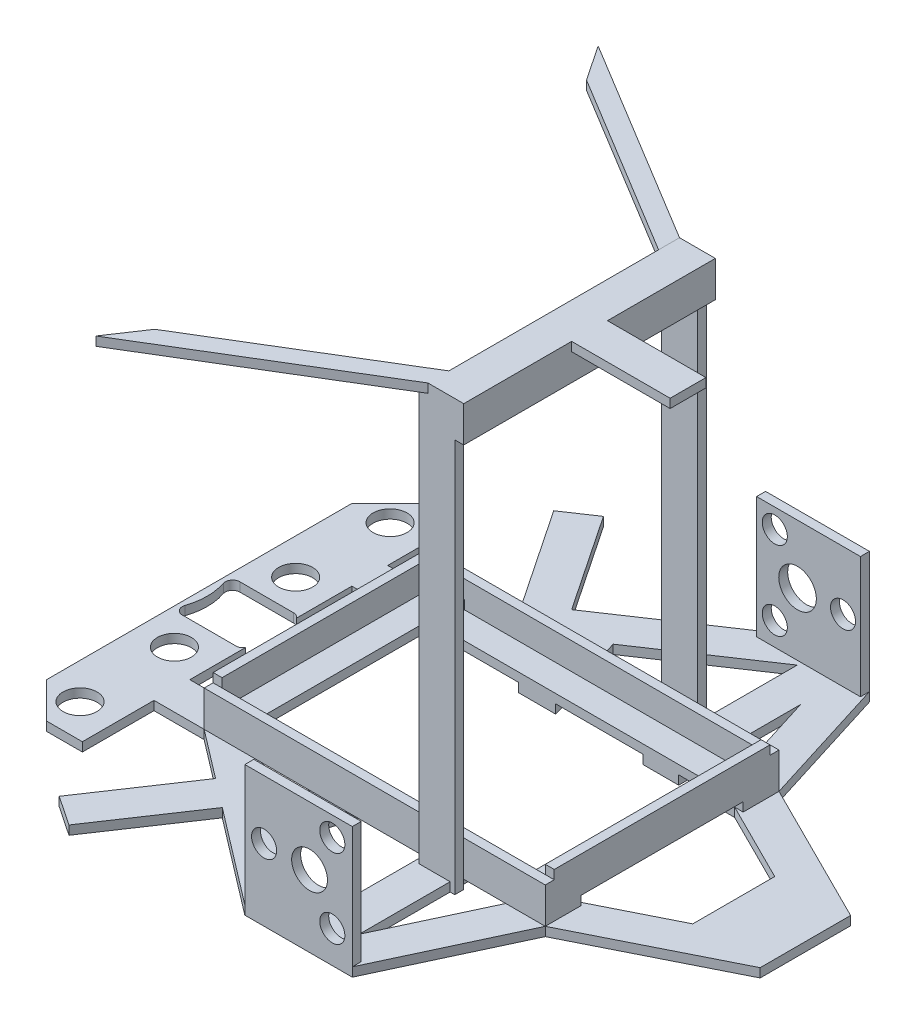
SolidWorks part; units mm, degrees
material "Galvanized Steel"
ref_plane "Front Plane" through (0, 0, 0) normal (0, 0, 1) x (1, 0, 0)
ref_plane "Top Plane" through (0, 0, 0) normal (0, 1, 0) x (1, 0, 0)
ref_plane "Right Plane" through (0, 0, 0) normal (1, 0, 0) x (0, 0, -1)
sketch "Battery Front sketch" plane through (0, 0, 0) normal (0, 0, 1) x (1, 0, 0)
  line L0 (90.25, 144.5) -> (90.25, 4) construction
  line L1 (90.25, 15) -> (95.25, 15)
  line L2 (90.25, 15) -> (90.25, -5)
  line L3 (90.25, -5) -> (95.25, -5)
  line L4 (95.25, 15) -> (95.25, -5)
  line L5 (86.25, 0) -> (-86.25, 0) construction
  line L6 (75.25, 0) -> (95.25, 0)
  line L7 (75.25, 0) -> (75.25, -5)
  line L8 (75.25, -5) -> (95.25, -5)
  line L9 (95.25, 0) -> (95.25, -5)
  dimension "D1" = 20
  dimension "D2" = 20
  dimension "D3" = 5
  dimension "D4" = 5
extrude "Battery Front" add sketch "Battery Front sketch" against normal up to surface (120.5 mm away) contours L3 L2 L1 L4 | L8 L7 L6 L9
sketch "Battery Rear Sketch" plane through (0, 0, -120.5) normal (0, 0, -1) x (-1, 0, 0)
  line L0 (90.25, 144.5) -> (90.25, 4) construction
  line L1 (90.25, 15) -> (95.25, 15)
  line L2 (90.25, 15) -> (90.25, -5)
  line L3 (90.25, -5) -> (95.25, -5)
  line L4 (95.25, 15) -> (95.25, -5)
  line L5 (86.25, 0) -> (-86.25, 0) construction
  line L6 (75.25, 0) -> (95.25, 0)
  line L7 (75.25, 0) -> (75.25, -5)
  line L8 (75.25, -5) -> (95.25, -5)
  line L9 (95.25, 0) -> (95.25, -5)
  dimension "D1" = 5
  dimension "D2" = 5
  dimension "D3" = 20
  dimension "D4" = 20
extrude "Battery Rear" add sketch "Battery Rear Sketch" against normal up to surface (120.5 mm away) separate body contours L2 L6 L4 L1 | L8 L7 L6 L9 | L4 L1 L2 L3 region at (-92.75, 7.5, -120.5)
sketch "Battery Side Sketch" plane through (-95.25, 0, 0) normal (-1, 0, 0) x (0, 0, 1)
  line L0 (0, 144.5) -> (0, 4) construction
  line L1 (0, 10) -> (5, 10)
  line L2 (0, 10) -> (0, -10)
  line L3 (0, -10) -> (5, -10)
  line L4 (5, 10) -> (5, -10)
  line L5 (0, -5) -> (-120.5, -5) construction
  line L6 (5, -10) -> (-15, -10)
  line L7 (5, -10) -> (5, -5)
  line L8 (5, -5) -> (-15, -5)
  line L9 (-15, -10) -> (-15, -5)
  line L10 (-120.5, 15) -> (-120.5, -5) construction
  line L11 (-120.5, 10) -> (-125.5, 10)
  line L12 (-120.5, 10) -> (-120.5, -10)
  line L13 (-120.5, -10) -> (-125.5, -10)
  line L14 (-125.5, 10) -> (-125.5, -10)
  line L16 (-105.5, -5) -> (-125.5, -5)
  line L17 (-105.5, -5) -> (-105.5, -10)
  line L18 (-105.5, -10) -> (-125.5, -10)
  line L19 (-125.5, -5) -> (-125.5, -10)
  line M10 (-120.5, -5) -> (0, -5)
  dimension "D1" = 20
  dimension "D2" = 20
  dimension "D3" = 20
  dimension "D4" = 20
  dimension "D5" = 5
  dimension "D6" = 5
  dimension "D7" = 5
  dimension "D8" = 5
extrude "Battery Side" add sketch "Battery Side Sketch" against normal up to surface (190.5 mm away) contours L9 L6 L2 M10 | L3 L2 L1 L4 | L14 L11 L12 L13 | L18 L17 L16 L19 region at (-95.25, -7.5, -7.5) up to face at (95.25, 5, -60.25)
sketch "Left Motor Attach Sketch" plane through (0, 0, -194) normal (0, 0, -1) x (-1, 0, 0)
  line L0 (-95.25, -10) -> (95.25, -10) construction
  line L1 (-14.2679, -10) -> (-72.2679, -10)
  line L2 (-14.2679, -10) -> (-14.2679, 57.8525)
  line L3 (-14.2679, 57.8525) -> (-72.2679, 57.8525)
  line L4 (-72.2679, -10) -> (-72.2679, 57.8525)
  arc A0 (-32.3069, 57.4983) -> (-39.0041, 57.7983) centre (-37.1179, 25.0025) ccw construction
  circle A1 centre (-24.4179, 46.9995) radius 7
  circle A2 centre (-62.5179, 25.0025) radius 7
  circle A3 centre (-24.4179, 3.0054) radius 7
  circle A4 centre (-37.1179, 25.0025) radius 10.5
  circle A5 centre (-24.4179, 46.9995) radius 4.8649 construction
  circle A6 centre (-62.5179, 25.0025) radius 4.8649 construction
  dimension "D3" = 14
  dimension "D4" = 14
  dimension "D5" = 14
  dimension "D6" = 21
  dimension "D1" = 58
  dimension "D2" = 10
extrude "Left Motor Attach" add sketch "Left Motor Attach Sketch" along normal blind 5 separate body
sketch "Right Motor Attach Sketch" plane through (0, 0, 73.5) normal (0, 0, 1) x (1, 0, 0)
  line L0 (95.25, -10) -> (-95.25, -10) construction
  line L1 (0.9679, -10) -> (60.9679, -10)
  line L2 (0.9679, -10) -> (0.9679, 57.8525)
  line L3 (0.9679, 57.8525) -> (60.9679, 57.8525)
  line L4 (60.9679, -10) -> (60.9679, 57.8525)
  line L5 (14.2679, 57.8525) -> (72.2679, 57.8525) construction
  circle A0 centre (49.8179, 46.9995) radius 7
  circle A1 centre (49.8179, 3.0054) radius 7
  circle A2 centre (11.7179, 25.0025) radius 7
  circle A3 centre (11.7179, 25.0025) radius 4.8649 construction
  circle A4 centre (37.1179, 25.0025) radius 10
  dimension "D1" = 14
  dimension "D2" = 14
  dimension "D3" = 14
  dimension "D4" = 20
  dimension "D5" = 60
  dimension "D6" = 9
extrude "Right Motor Attach" add sketch "Right Motor Attach Sketch" along normal blind 5 separate body
sketch "Support Sketch" plane through (0, -10, 0) normal (0, -1, 0) x (-1, 0, 0)
  line L0 (-14.2679, 199) -> (95.25, 125.5)
  line L1 (-95.25, 125.5) -> (95.25, 125.5) construction
  line L4 (89.1609, 105.5) -> (-50.1578, 199)
  line L5 (-72.2679, 199) -> (-14.2679, 199) construction
  line L6 (-50.1578, 199) -> (-14.2679, 199)
  line L7 (89.1609, 105.5) -> (95.25, 105.5)
  line L8 (95.25, 105.5) -> (95.25, 125.5)
  line L9 (-95.25, 105.5) -> (95.25, 105.5) construction
  line L10 (95.25, -5) -> (-0.9679, -78.5)
  line L11 (-0.9679, -78.5) -> (-33.9145, -78.5)
  line L12 (-0.9679, -78.5) -> (-60.9679, -78.5) construction
  line L13 (-33.9145, -78.5) -> (88.4851, 15)
  line L14 (-95.25, 15) -> (95.25, 15) construction
  line L15 (88.4851, 15) -> (95.25, 15)
  line L16 (95.25, 15) -> (95.25, -5)
  dimension "D1" = 20
  dimension "D2" = 20
extrude "Support" add sketch "Support Sketch" along normal blind 5
sketch "Support to motor sketch 1" plane through (0, -10, 0) normal (0, -1, 0) x (-1, 0, 0)
  line L0 (-60.9679, -78.5) -> (-95.25, -5)
  line L1 (-95.25, -5) -> (-95.25, 15)
  line L2 (-82.5099, 15) -> (-38.8993, -78.5)
  line L3 (-95.25, 15) -> (88.4851, 15) construction
  line L4 (-0.9679, -78.5) -> (-60.9679, -78.5) construction
  line L5 (-38.8993, -78.5) -> (-60.9679, -78.5)
  line L6 (-95.25, 15) -> (-82.5099, 15)
  line L7 (-95.25, 125.5) -> (-72.2679, 199)
  line L8 (-72.2679, 199) -> (-51.313, 199)
  line L9 (-72.2679, 199) -> (-50.1578, 199) construction
  line L10 (-51.313, 199) -> (-80.5487, 105.5)
  line L11 (-95.25, 105.5) -> (89.1609, 105.5) construction
  line L12 (-80.5487, 105.5) -> (-95.25, 105.5)
  line L13 (-95.25, 105.5) -> (-95.25, 125.5)
  dimension "D1" = 20
  dimension "D2" = 20
extrude "Support to motor 1" add sketch "Support to motor sketch 1" along normal blind 5
sketch "Support to motor sketch 2" plane through (0, -10, 0) normal (0, -1, 0) x (-1, 0, 0)
  line L0 (-47.1179, -78.5) -> (-27.1179, -78.5)
  line L1 (-33.9145, -78.5) -> (-0.9679, -78.5) construction
  line L3 (-14.2679, 199) -> (-50.1578, 199) construction
  line L4 (-39.2679, 199) -> (-59.2679, 199)
  line L5 (-47.1179, -78.5) -> (-47.1179, 15)
  line L7 (-51.313, 199) -> (-72.2679, 199) construction
  line L8 (-82.5099, 15) -> (88.4851, 15) construction
  line L9 (-47.1179, 15) -> (-27.1179, 15)
  line L10 (-27.1179, 15) -> (-27.1179, -78.5)
  line L11 (-59.2679, 199) -> (-59.2679, 105.5)
  line L12 (-80.5487, 105.5) -> (89.1609, 105.5) construction
  line L13 (-59.2679, 105.5) -> (-39.2679, 105.5)
  line L14 (-39.2679, 105.5) -> (-39.2679, 199)
  dimension "D1" = 20
  dimension "D2" = 13
  dimension "D3" = 20
extrude "Support to motor 2" add sketch "Support to motor sketch 2" along normal blind 5
sketch "Side Support sketch" plane through (0, -10, 0) normal (0, -1, 0) x (-1, 0, 0)
  line L0 (30.6226, -54.3683) -> (9.3289, 15)
  line L1 (-0.9679, -78.5) -> (95.25, -5) construction
  line L2 (-27.1179, 15) -> (88.4851, 15) construction
  line L3 (9.3289, 15) -> (30.25, 15)
  line L4 (30.25, 15) -> (47.5698, -41.4225)
  line L5 (47.5698, -41.4225) -> (30.6226, -54.3683)
  line L6 (9.4587, 105.5) -> (27.9675, 170.6548)
  line L7 (-39.2679, 105.5) -> (89.1609, 105.5) construction
  line L8 (95.25, 125.5) -> (-14.2679, 199) construction
  line L9 (27.9675, 170.6548) -> (45.4297, 158.9356)
  line L10 (45.4297, 158.9356) -> (30.25, 105.5)
  line L11 (30.25, 105.5) -> (9.4587, 105.5)
  dimension "D1" = 20
  dimension "D2" = 20
  dimension "D3" = 65
  dimension "D4" = 60
  dimension "D5" = 65
  dimension "D6" = 60
extrude "Side Support" add sketch "Side Support sketch" along normal blind 5
sketch "Sensor Array sketch" plane through (0, -14.9782, 0) normal (0, 1, 0) x (1, 0, 0)
  line L6 (80.5487, 105.5) -> (59.2679, 105.5) construction
  line L7 (82.5099, 15) -> (47.1179, 15) construction
  line L8 (95.25, 105.5) -> (95.25, 15) construction
  line L14 (-95.25, 105.5) -> (-123.25, 105.5)
  line L15 (-95.25, 125.5) -> (-163.25, 125.5)
  line L16 (-95.25, 15) -> (-123.25, 15)
  line L17 (-123.25, 15) -> (-123.25, 105.5)
  line L18 (-163.25, 125.5) -> (-163.25, -5)
  line L19 (-163.25, -5) -> (-95.25, -5)
  line L20 (-95.25, 15) -> (-95.25, 105.5) construction
  line L22 (-163.25, 125.5) -> (-123.25, 125.5)
  line L23 (-95.25, -5) -> (-95.25, 15)
  line L24 (-95.25, 105.5) -> (-95.25, 125.5)
  line L25 (95.25, -5) -> (175.25, 37.6667)
  line L26 (175.25, 37.6667) -> (175.25, 82.8333)
  line L27 (175.25, 82.8333) -> (95.25, 125.5)
  line L28 (95.25, 125.5) -> (95.25, 105.5)
  line L29 (95.25, 105.5) -> (90.25, 105.5)
  line L30 (-163.25, 125.5) -> (-163.25, 165.5)
  line L31 (-163.25, 165.5) -> (-123.25, 165.5)
  line L32 (90.25, 105.5) -> (135.25, 81.5)
  line L33 (135.25, 81.5) -> (135.25, 39)
  line L34 (135.25, 39) -> (90.25, 15)
  line L35 (90.25, 15) -> (95.25, 15)
  line L36 (95.25, 15) -> (95.25, -5) construction
  line L37 (82.5099, 15) -> (95.25, 15) construction
  line L38 (95.25, 15) -> (95.25, -5)
  line L39 (-123.25, 125.5) -> (-123.25, 165.5)
  line L40 (-163.25, -5) -> (-123.25, -5)
  line L41 (-163.25, -5) -> (-163.25, -45)
  line L42 (-163.25, -45) -> (-123.25, -45)
  line L43 (-123.25, -5) -> (-123.25, -45)
  circle A0 centre (-143.25, 146.8192) radius 9.5
  circle A1 centre (-143.25, 94.1064) radius 9.5
  circle A2 centre (-143.25, 26.3936) radius 9.5
  circle A3 centre (-143.25, -26.3192) radius 9.5
  arc M11 (-160.5046, 49.5758) -> (-156.6164, 44.175) centre (-156.6164, 48.275) ccw
  line M12 (-156.6164, 44.175) -> (-126.6664, 44.175)
  arc M13 (-126.6664, 44.175) -> (-122.7783, 49.5758) centre (-126.6664, 48.275) ccw
  arc M15 (-122.7783, 70.9242) -> (-126.6664, 76.325) centre (-126.6664, 72.225) ccw
  line M16 (-126.6664, 76.325) -> (-156.6164, 76.325)
  arc M17 (-156.6164, 76.325) -> (-160.5046, 70.9242) centre (-156.6164, 72.225) ccw
  arc M18 (-160.5046, 70.9242) -> (-160.5046, 49.5758) centre (-192.4108, 60.25) cw
  dimension "D12" = 19
  dimension "D13" = 19
  dimension "D14" = 19
  dimension "D15" = 19
  dimension "D1" = 40
  dimension "D2" = 28
  dimension "D3" = 20
  dimension "D4" = 20
  dimension "D5" = 40
  dimension "D6" = 40
  dimension "D7" = 5
  dimension "D8" = 5
  dimension "D9" = 90.5
  dimension "D10" = 40
  dimension "D11" = 40
extrude "Sensor Array" add sketch "Sensor Array sketch" along normal blind 5 contours L15 L39 L31 L30 | L14 L24 L15 L18 L19 L23 L16 L17 M13 M12 M11 M18 M17 M16 M15 | L43 L19 L41 L42 region at (-109.25, -14.9782, -106.9715) region at (-143.25, -14.9782, -126.0657) region at (-143.25, -14.9782, 5.5657)
sketch "Vertical Support sketch" plane through (0, 0, -125.5) normal (0, 0, -1) x (-1, 0, 0)
  line L0 (-14.2679, -15) -> (-72.2679, -15) construction
  line L1 (-29.7174, -15) -> (-49.7174, -15)
  line L2 (-29.7174, -15) -> (-29.7174, 220)
  line L3 (-29.7174, 220) -> (-49.7174, 220)
  line L4 (-49.7174, -15) -> (-49.7174, 220)
  line L5 (-97.7174, 133.32) -> (-97.7174, 68.7025) construction
  dimension "D1" = 20
  dimension "D2" = 48
  dimension "D3" = 235
extrude "Vertical Support" add sketch "Vertical Support sketch" along normal blind 5
ref_plane "Mid Plane" through (-85.3065, -17.6006, -60.25) normal (0, 0, -1) x (-1, 0, 0)
mirror "Other Vertical Support" about plane through (-85.3065, -17.6006, -60.25) normal (0, 0, -1) of "Vertical Support"
sketch "Horizontal Support Sketch" plane through (0, 0, -130.5) normal (0, 0, -1) x (-1, 0, 0)
  line L0 (-49.7174, 220) -> (-49.7174, -10) construction
  line L1 (-49.7174, 205) -> (-54.7174, 205)
  line L2 (-49.7174, 205) -> (-49.7174, 225)
  line L3 (-49.7174, 225) -> (-54.7174, 225)
  line L4 (-54.7174, 205) -> (-54.7174, 225)
  line L5 (-29.7174, 220) -> (-49.7174, 220) construction
  line L6 (-54.7174, 225) -> (-34.7174, 225)
  line L7 (-54.7174, 225) -> (-54.7174, 220)
  line L8 (-54.7174, 220) -> (-34.7174, 220)
  line L9 (-34.7174, 225) -> (-34.7174, 220)
  line M9 (-29.7174, 220) -> (-49.7174, 220)
  line M10 (-49.7174, 220) -> (-49.7174, -10)
  dimension "D1" = 20
  dimension "D2" = 20
  dimension "D3" = 5
  dimension "D4" = 5
extrude "Horizontal Support" add sketch "Horizontal Support Sketch" against normal up to surface (140.5 mm away) contours L9 L6 L2 M9 | L4 L8 L2 L3 | L8 L4 L1 M10 region at (52.2174, 212.5, -130.5) region at (52.2174, 222.5, -130.5) region at (42.2174, 222.5, -130.5) up to face at (42.1842, 65, 10)
sketch "Support for bars sketch1" plane through (0, 225, 0) normal (0, 1, 0) x (1, 0, 0)
  line L0 (34.7174, -10) -> (34.7174, 130.5) construction
  line L1 (34.7174, 70.25) -> (109.7174, 70.25)
  line L2 (34.7174, 70.25) -> (34.7174, 50.25)
  line L3 (34.7174, 50.25) -> (109.7174, 50.25)
  line L4 (109.7174, 70.25) -> (109.7174, 50.25)
  line L5 (-8.0315, 60.25) -> (-162.5815, 60.25) construction
  dimension "D1" = 20
  dimension "D2" = 10
  dimension "D3" = 75
extrude "Support for bars1" add sketch "Support for bars sketch1" against normal blind 5
sketch "Support for bars sketch2" plane through (0, -10, 0) normal (0, 1, 0) x (1, 0, 0)
  line L0 (-39.3893, 138.9029) -> (-86.7564, 209.4816)
  line L1 (-39.6829, 138.7058) -> (-59.3601, 125.5) construction
  line L2 (-103.3631, 198.3364) -> (-55.9961, 127.7577)
  line L3 (-55.9961, 127.7577) -> (-39.3893, 138.9029)
  line L4 (-86.7564, 209.4816) -> (-103.3631, 198.3364)
  dimension "D1" = 20
  dimension "D2" = 33.8521
  dimension "D3" = 85
extrude "Support for bars2" add sketch "Support for bars sketch2" against normal blind 5
mirror "Support for bars3" about plane through (-85.3065, -17.6006, -60.25) normal (0, 0, -1) of "Support for bars2"
sketch "Support for bars sketch4" plane through (0, 225, 0) normal (0, 1, 0) x (1, 0, 0)
  line L0 (34.7174, 130.5) -> (-80.7223, 200.4906)
  line L1 (-50.5345, 155.5096) -> (-86.7564, 209.4816) construction
  line L2 (-80.7223, 200.4906) -> (-67.5101, 180.7857)
  line L3 (-67.5101, 180.7857) -> (34.7174, 118.8056)
  line L4 (34.7174, -10) -> (34.7174, 130.5) construction
  line L5 (34.7174, 118.8056) -> (34.7174, 130.5)
  circle A0 centre (-81.75, 185.5) radius 15 construction
  dimension "D1" = 10
  dimension "D2" = 135
extrude "Support for bars4" add sketch "Support for bars sketch4" against normal blind 5 separate body
mirror "Support for bars sketch5" about plane through (-85.3065, -17.6006, -60.25) normal (0, 0, -1) of "Support for bars4"
chamfer "Array chamfer1" distance 20 angle 45 1 edges at (-163.25, -12.4782, -165.5)
chamfer "Array champer2" distance 20 angle 45 1 edges at (-163.25, -12.4782, 45)
sketch "Front Caster support sketch" plane through (0, -15, 0) normal (0, -1, 0) x (1, 0, 0)
  line L0 (95.25, 5) -> (175.25, -35)
  line L1 (175.25, -35) -> (175.25, -85.5)
  line L2 (175.25, -85.5) -> (95.25, -125.5)
  line L3 (95.25, -125.5) -> (95.25, -105.5)
  line L4 (95.25, -105.5) -> (90.5286, -105.5)
  line L5 (95.25, -105.5) -> (95.25, -15) construction
  line L6 (90.5286, -105.5) -> (135.25, -83.1393)
  line L7 (135.25, -83.1393) -> (135.25, -37.3607)
  line L8 (135.25, -37.3607) -> (90.5286, -15)
  line L9 (82.5099, -15) -> (95.25, -15) construction
  line L10 (90.5286, -15) -> (95.25, -15)
  line L11 (95.25, -15) -> (95.25, 5) construction
  line L12 (95.25, -15) -> (95.25, 5)
  point P16 (112.8893, -26.1803)
  dimension "D1" = 20
  dimension "D2" = 20
  dimension "D3" = 40
  dimension "D4" = 40
  dimension "D5" = 50
extrude "Front Caster support" add sketch "Front Caster support sketch" against normal blind 5
